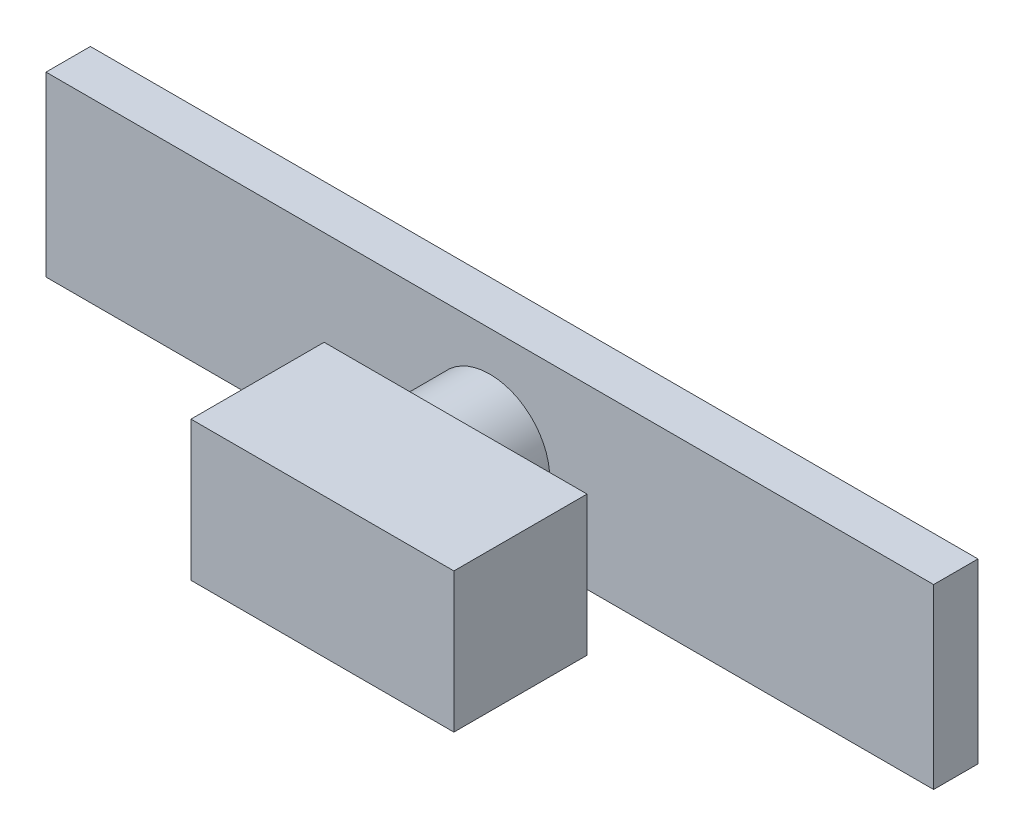
SolidWorks part; units mm, degrees
ref_plane "Front Plane" through (0, 0, 0) normal (0, 0, 1) x (1, 0, 0)
ref_plane "Top Plane" through (0, 0, 0) normal (0, 1, 0) x (1, 0, 0)
ref_plane "Right Plane" through (0, 0, 0) normal (1, 0, 0) x (0, 0, -1)
sketch "Sketch2" plane through (0, 0, 0) normal (0, 0, 1) x (1, 0, 0)
  line L1 (-47.8692, 21.2481) -> (206.1308, 21.2481)
  line L2 (-47.8692, 21.2481) -> (-47.8692, 8.5481)
  line L3 (-47.8692, 8.5481) -> (206.1308, 8.5481)
  line L4 (206.1308, 21.2481) -> (206.1308, 8.5481)
  dimension "D1" = 12.7
  dimension "D2" = 254
extrude "Boss-Extrude1" add sketch "Sketch2" along normal blind 50.8
sketch "Sketch3" plane through (0, 21.2481, 0) normal (0, 1, 0) x (1, 0, 0)
  circle A0 centre (79.1308, -28.4831) radius 17.1408
extrude "Boss-Extrude2" add sketch "Sketch3" along normal blind 19.05
sketch "Sketch4" plane through (0, 40.2981, 0) normal (0, 1, 0) x (1, 0, 0)
  line L1 (50.7675, -8.111) -> (126.0034, -8.111)
  line L2 (50.7675, -8.111) -> (50.7675, -48.0661)
  line L3 (50.7675, -48.0661) -> (126.0034, -48.0661)
  line L4 (126.0034, -8.111) -> (126.0034, -48.0661)
extrude "Boss-Extrude3" add sketch "Sketch4" along normal blind 38.1
scale "Scale2" scale about centroid uniform scaling yes scale factor 0.06
move or copy body "Body-Move/Copy1" bodies to move or copy 105 copy no rotation origin (0, 33.6669, 26.5501) rotation axis (1, 0, 0) rotation angle 90
move or copy body "Body-Move/Copy3" bodies to move or copy 106 copy no translate (-50.8, 0, -50.8)
scale "Scale5" scale about centroid uniform scaling yes scale factor 0.25
move or copy body "Body-Move/Copy9" bodies to move or copy 111 copy no translate (-50.8, 0, 0)
move or copy body "Body-Move/Copy13" bodies to move or copy 117 copy no translate (0, -50.8, 0)
scale "Scale6" bodies to scale 121 scale about centroid uniform scaling yes scale factor 0.25
move or copy body "Body-Move/Copy16" bodies to move or copy 122 copy no translate (0, 0, -12.7)
move or copy body "Body-Move/Copy17" bodies to move or copy 125 copy no translate (0, 0, -76.2)
move or copy body "Body-Move/Copy18" bodies to move or copy 126 copy no translate (0, 0, -254)
